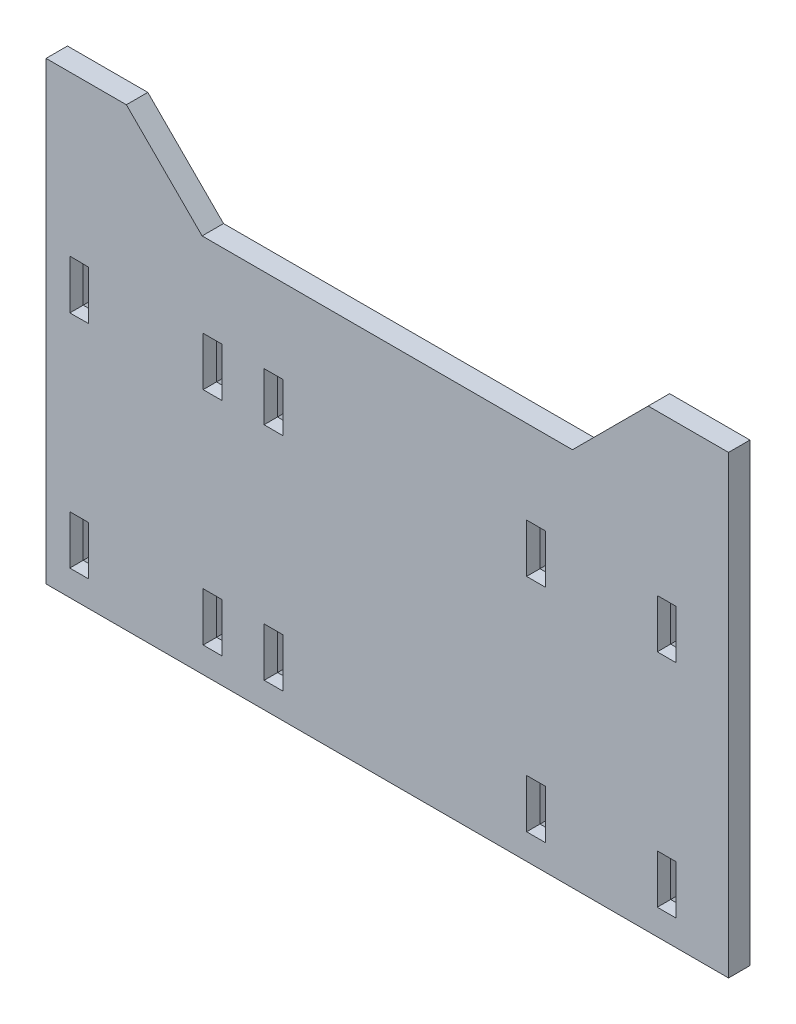
SolidWorks part; units mm, degrees
ref_plane "Front Plane" through (0, 0, 0) normal (0, 0, 1) x (1, 0, 0)
ref_plane "Top Plane" through (0, 0, 0) normal (0, 1, 0) x (1, 0, 0)
ref_plane "Right Plane" through (0, 0, 0) normal (1, 0, 0) x (0, 0, -1)
sketch "Sketch1" plane through (0, 0, 0) normal (0, 0, 1) x (1, 0, 0)
  line L6 (-34.3851, 25.207) -> (-30.8551, 25.207)
  line L7 (26.0149, 25.207) -> (29.5449, 25.207)
  line L8 (26.0149, 25.207) -> (26.0149, 16.093)
  line L9 (26.0149, 16.093) -> (29.5449, 16.093)
  line L10 (29.5449, 25.207) -> (29.5449, 16.093)
  line L12 (26.0149, -16.093) -> (29.5449, -16.093)
  line L13 (26.0149, -25.207) -> (26.0149, -16.093)
  line L14 (29.5449, -25.207) -> (29.5449, -16.093)
  line L15 (26.0149, -25.207) -> (29.5449, -25.207)
  line L16 (-19.4551, 25.207) -> (-22.9851, 25.1844)
  line L17 (-19.4551, 25.207) -> (-19.4406, 16.093)
  line L18 (-22.9851, 25.1844) -> (-22.9996, 16.1156)
  line L19 (-19.4406, 16.093) -> (-22.9996, 16.1156)
  line L20 (-19.4551, -16.093) -> (-22.9851, -16.093)
  line L21 (-19.4551, -25.207) -> (-19.4551, -16.093)
  line L22 (-22.9851, -25.207) -> (-22.9851, -16.093)
  line L23 (-19.4551, -25.207) -> (-22.9851, -25.207)
  line L39 (50.4149, 25.207) -> (53.9449, 25.207)
  line L40 (50.4149, 25.207) -> (50.4149, 16.093)
  line L41 (50.4149, 16.093) -> (53.9449, 16.093)
  line L42 (53.9449, 25.207) -> (53.9449, 16.093)
  line L43 (50.4149, -16.093) -> (53.9449, -16.093)
  line L44 (50.4149, -16.093) -> (50.4149, -25.207)
  line L45 (50.4149, -25.207) -> (53.9449, -25.207)
  line L46 (53.9449, -16.093) -> (53.9449, -25.207)
  line L47 (-34.3851, 25.207) -> (-34.3851, 16.093)
  line L48 (-34.3851, 16.093) -> (-30.8551, 16.093)
  line L49 (-30.8551, 25.207) -> (-30.8551, 16.093)
  line L50 (-34.3851, -16.093) -> (-30.8551, -16.093)
  line L51 (-34.3851, -16.093) -> (-34.3851, -25.207)
  line L52 (-34.3851, -25.207) -> (-30.8551, -25.207)
  line L53 (-30.8551, -16.093) -> (-30.8551, -25.207)
  line L60 (-59.285, 25.25) -> (-55.7552, 25.207)
  line L61 (-59.285, 25.25) -> (-59.285, 16.05)
  line L62 (-59.285, 16.05) -> (-55.7552, 16.093)
  line L63 (-55.7552, 25.207) -> (-55.7552, 16.093)
  line L64 (-59.2851, -16.093) -> (-55.7551, -16.093)
  line L65 (-59.2851, -16.093) -> (-59.2851, -25.207)
  line L66 (-59.2851, -25.207) -> (-55.7551, -25.207)
  line L67 (-55.7551, -16.093) -> (-55.7551, -25.207)
  line L80 (-63.7201, 30) -> (63.7201, 30)
  line L81 (63.7201, 30) -> (63.7201, -30)
  line L82 (52.1799, 25.207) -> (52.1799, 16.093) construction
  line L83 (27.7799, 16.093) -> (27.7799, 25.207) construction
  line L84 (-63.7201, 30) -> (-63.7201, -30)
  line L85 (-63.7201, -30) -> (63.7201, -30)
  line L87 (53.2799, 20.65) -> (50.4149, 20.65) construction
  line L88 (29.5449, 20.65) -> (26.0149, 20.65) construction
  line L89 (53.9449, -20.65) -> (50.4149, -20.65) construction
  line L90 (52.1799, -16.093) -> (52.1799, -25.207) construction
  line L91 (27.7799, -16.093) -> (27.7799, -25.207) construction
  line L92 (29.5449, -20.65) -> (26.0149, -20.65) construction
  line L93 (-19.4551, -20.65) -> (-22.9851, -20.65) construction
  line L94 (-21.2201, -16.093) -> (-21.2201, -25.207) construction
  line L95 (-32.6201, -16.093) -> (-32.6201, -25.207) construction
  line L96 (-30.8551, -20.65) -> (-34.3851, -20.65) construction
  line L97 (-55.7551, -20.65) -> (-59.2851, -20.65) construction
  line L98 (-57.5201, -16.093) -> (-57.5201, -25.207) construction
  line L99 (-57.5201, 25.2285) -> (-57.5201, 16.0715) construction
  line L100 (-32.6201, 25.207) -> (-32.6201, 16.093) construction
  line L101 (-21.2201, 25.1957) -> (-21.2201, 16.1043) construction
  line L102 (-55.7552, 20.65) -> (-59.285, 20.65) construction
  line L103 (-34.3851, 20.65) -> (-30.8551, 20.65) construction
  line L104 (-19.4479, 20.65) -> (-22.9923, 20.65) construction
  point P0 (0, 0)
  point P86 (0, 30)
  point P87 (63.7201, 0)
  dimension "D1" = 9.2
  dimension "D2" = 3.53
  dimension "D3" = 127.4402
  dimension "D4" = 60
  dimension "D7" = 11.4
  dimension "D8" = 24.4
  dimension "D5" = 27.7799
  dimension "D6" = 21.2201
  dimension "D10" = 20.65
  dimension "D11" = 20.65
  dimension "D9" = 24.9
extrude "Boss-Extrude1" add sketch "Sketch1" against normal blind 4
sketch "Sketch2" plane through (0, 0, 0) normal (0, 0, 1) x (1, 0, 0)
  line L0 (-63.7201, 30) -> (-63.7201, 55)
  line L1 (-63.7201, 55) -> (-48.7201, 55)
  line L2 (-48.7201, 55) -> (-34.578, 40.8579)
  line L7 (63.7201, 30) -> (-63.7201, 30)
  line L8 (48.7201, 55) -> (63.7201, 55)
  line L9 (63.7201, 55) -> (63.7201, 30)
  line L10 (48.7201, 55) -> (34.578, 40.8579)
  line L11 (34.578, 40.8579) -> (-34.578, 40.8579)
  line L12 (-63.7201, 30) -> (-63.7201, -30) construction
  line L14 (63.7201, -30) -> (63.7201, 30) construction
  dimension "D1" = 25
  dimension "D2" = 15
  dimension "D3" = 135
  dimension "D4" = 20
extrude "Boss-Extrude2" add sketch "Sketch2" against normal blind 4
chamfer "Chamfer1" distance 1.5 distance2 0.5 40 edges at (27.7799, 16.093, -4) (29.5449, 20.65, -4) (26.0149, 20.65, -4) (27.7799, 25.207, -4) (53.9449, 20.65, -4) (52.1799, 16.093, -4) (50.4149, 20.65, -4) (52.1799, 25.207, -4) (52.1799, -25.207, -4) (53.9449, -20.65, -4) (52.1799, -16.093, -4) (50.4149, -20.65, -4) (29.5449, -20.65, -4) (27.7799, -25.207, -4) (26.0149, -20.65, -4) (27.7799, -16.093, -4) (-21.2201, -25.207, -4) (-19.4551, -20.65, -4) (-21.2201, -16.093, -4) (-22.9851, -20.65, -4) (-30.8551, -20.65, -4) (-32.6201, -25.207, -4) (-34.3851, -20.65, -4) (-32.6201, -16.093, -4) (-55.7551, -20.65, -4) (-57.5201, -16.093, -4) (-59.2851, -20.65, -4) (-57.5201, -25.207, -4) (-21.2201, 25.1957, -4) (-19.4479, 20.65, -4) (-21.2201, 16.1043, -4) (-22.9923, 20.65, -4) (-32.6201, 16.093, -4) (-30.8551, 20.65, -4) (-32.6201, 25.207, -4) (-34.3851, 20.65, -4) (-57.5201, 16.0715, -4) (-55.7552, 20.65, -4) (-57.5201, 25.2285, -4) (-59.285, 20.65, -4) first distance on face at (27.7799, 16.093, -2) first distance on face at (29.5449, 20.65, -2) first distance on face at (26.0149, 20.65, -2) first distance on face at (27.7799, 25.207, -2) first distance on face at (53.9449, 20.65, -2) first distance on face at (52.1799, 16.093, -2) first distance on face at (50.4149, 20.65, -2) first distance on face at (52.1799, 25.207, -2) first distance on face at (52.1799, -25.207, -2) first distance on face at (53.9449, -20.65, -2) first distance on face at (52.1799, -16.093, -2) first distance on face at (50.4149, -20.65, -2) first distance on face at (29.5449, -20.65, -2) first distance on face at (27.7799, -25.207, -2) first distance on face at (26.0149, -20.65, -2) first distance on face at (27.7799, -16.093, -2) first distance on face at (-21.2201, -25.207, -2) first distance on face at (-19.4551, -20.65, -2) first distance on face at (-21.2201, -16.093, -2) first distance on face at (-22.9851, -20.65, -2) first distance on face at (-30.8551, -20.65, -2) first distance on face at (-32.6201, -25.207, -2) first distance on face at (-34.3851, -20.65, -2) first distance on face at (-32.6201, -16.093, -2) first distance on face at (-55.7551, -20.65, -2) first distance on face at (-57.5201, -16.093, -2) first distance on face at (-59.2851, -20.65, -2) first distance on face at (-57.5201, -25.207, -2) first distance on face at (-21.2201, 25.1957, -2) first distance on face at (-19.4479, 20.65, -2) first distance on face at (-21.2201, 16.1043, -2) first distance on face at (-22.9923, 20.65, -2) first distance on face at (-32.6201, 16.093, -2) first distance on face at (-30.8551, 20.65, -2) first distance on face at (-32.6201, 25.207, -2) first distance on face at (-34.3851, 20.65, -2) first distance on face at (-57.5201, 16.0715, -2) first distance on face at (-55.7552, 20.65, -2) first distance on face at (-57.5201, 25.2285, -2) first distance on face at (-59.285, 20.65, -2)
equation "\"pin_hole_height\"=9.2"
equation "\"D1@Sketch1\"=\"pin_hole_height\""
equation "\"pin_hole_width\"=3.53"
equation "\"D2@Sketch1\"=\"pin_hole_width\""
equation "\"distancer\"=24.4"
